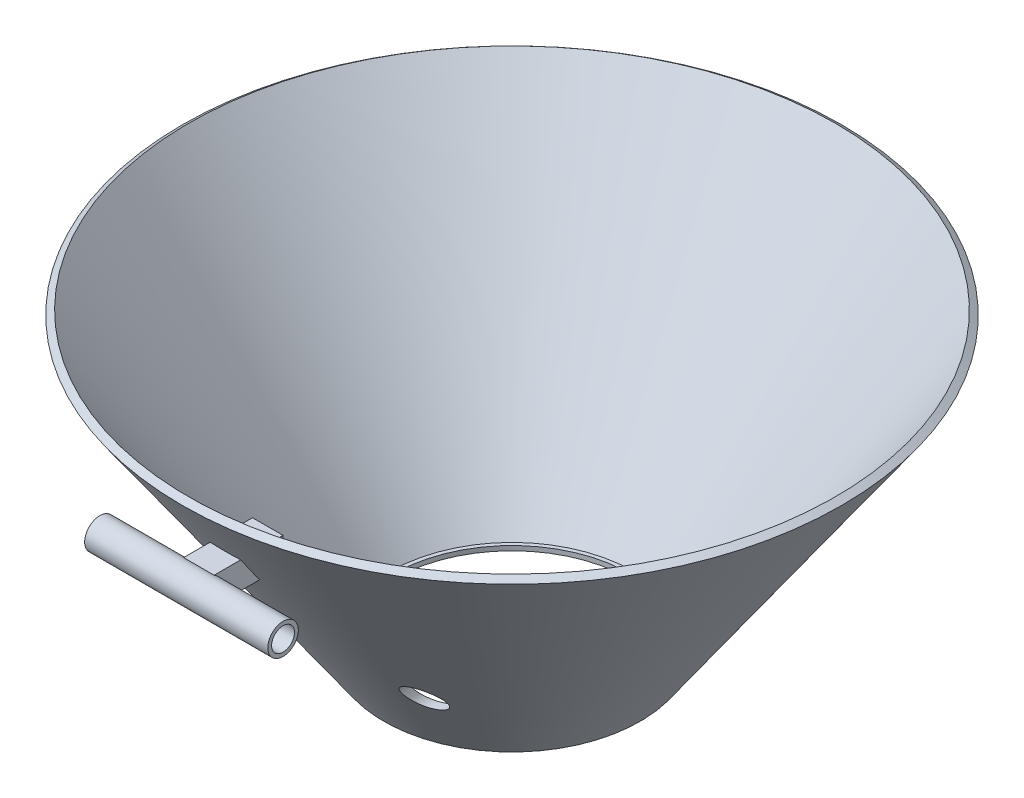
SolidWorks part; units mm, degrees
ref_plane "Front Plane" through (0, 0, 0) normal (0, 0, 1) x (1, 0, 0)
ref_plane "Top Plane" through (0, 0, 0) normal (0, 1, 0) x (1, 0, 0)
ref_plane "Right Plane" through (0, 0, 0) normal (1, 0, 0) x (0, 0, -1)
sketch "Sketch3" plane through (0, 0, 0) normal (0, 0, 1) x (1, 0, 0)
  line L0 (8.4003, 0) -> (21.6018, 18.8537)
  line L1 (0, 0) -> (8.4003, 0)
  line L2 (0, 0) -> (0, 0.3)
  line L3 (0, 0.3) -> (8, 0.3)
  line L4 (21.1923, 19.1405) -> (8, 0.3)
  line L5 (21.1923, 19.1405) -> (21.6018, 18.8537)
  dimension "D1" = 0.5
  dimension "D2" = 23
  dimension "D3" = 0.3
  dimension "D4" = 8
  dimension "D5" = 0.5
revolve "Revolve1" add sketch "Sketch3" angle 360 about L2
sketch "Sketch4" plane through (0, 0.3, 0) normal (0, 1, 0) x (1, 0, 0)
  circle A0 centre (0, 0) radius 7.75
  circle A1 centre (0, 0) radius 8 construction
  dimension "D1" = 0.25
extrude "Cut-Extrude1" cut sketch "Sketch4" against normal up to next
ref_axis "Axis2" through (0, 60.9449, 0) along (0, -1, 0)
ref_plane "Plane1" through (-5.6367, -3.9469, 0) normal (-0.8192, -0.5736, 0) x (0, 0, -1)
sketch "Sketch12" plane through (0, 0, 0) normal (0, 1, 0) x (1, 0, 0)
  circle A0 centre (0, 0) radius 20.5
  dimension "D1" = 41
sketch "Sketch13" plane through (0, 0, 0) normal (0, 0, 1) x (1, 0, 0)
  line L0 (0, 60.9449) -> (0, -49.0551) construction
  line L1 (1, 14.8537) -> (-1, 14.8537)
  line L2 (1, 14.8537) -> (1, 13.1026)
  line L3 (1, 13.1026) -> (-1, 13.1026)
  line L4 (-1, 14.8537) -> (-1, 13.1026)
  line L5 (1, 14.8537) -> (-1, 13.1026) construction
  line L6 (1, 13.1026) -> (-1, 14.8537) construction
  line L7 (21.6018, 18.8537) -> (-21.6018, 18.8537) construction
  point P0 (0, 13.9781)
  dimension "D1" = 4
extrude "Boss-Extrude1" add sketch "Sketch13" along normal blind 3 and the other way blind 2 from offset 18
sketch "Sketch14" plane through (-1, 0, 0) normal (-1, 0, 0) x (0, 0, 1)
  line L0 (21, 14.8537) -> (21, 13.1026) construction
  circle A0 centre (21, 13.9781) radius 1
extrude "Boss-Extrude2" add sketch "Sketch14" along normal blind 5 and the other way blind 7
sketch "Sketch15" plane through (-6, 0, 0) normal (-1, 0, 0) x (0, 0, 1)
  circle A0 centre (21, 13.9781) radius 0.75
extrude "Cut-Extrude2" cut sketch "Sketch15" against normal blind 15
sketch "Sketch16" plane through (0, 0, 0) normal (0, 0, 1) x (1, 0, 0)
  line L0 (0, 60.9449) -> (0, -49.0551) construction
  line L1 (20.5, 0) -> (-20.5, 0) construction
  circle A0 centre (-5, 5) radius 1
  circle A1 centre (5, 5) radius 1
  dimension "D1" = 5
  dimension "D2" = 5
  dimension "D3" = 5
  dimension "D4" = 5
extrude "Cut-Extrude3" cut sketch "Sketch16" along normal blind 20
